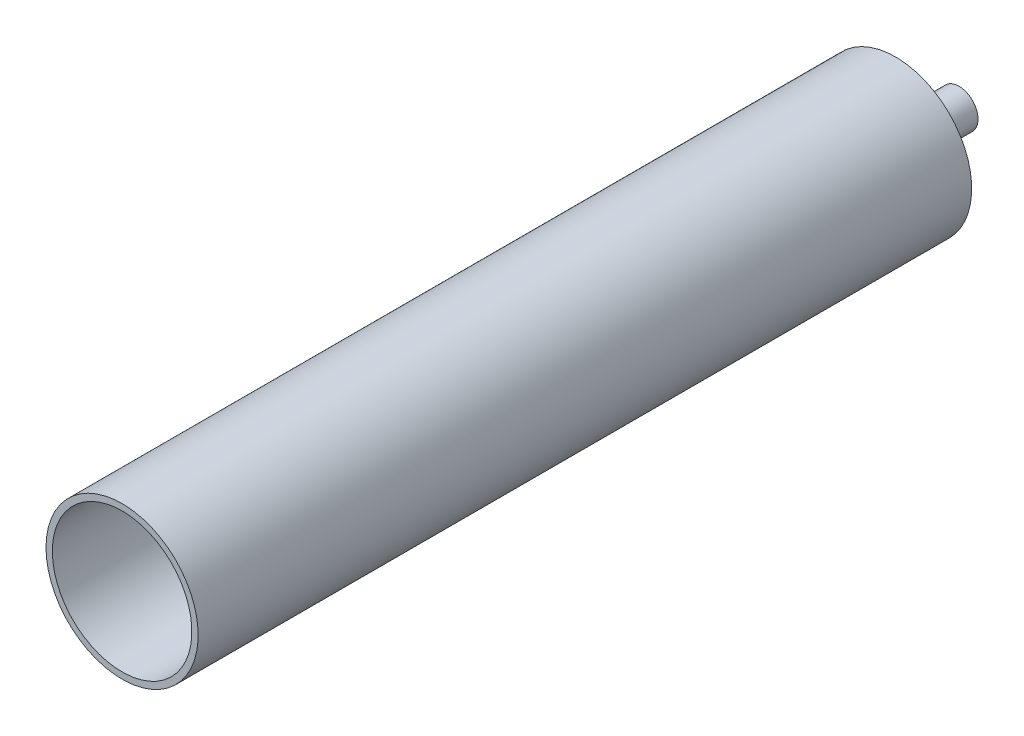
SolidWorks part; units mm, degrees
ref_plane "Front" through (0, 0, 0) normal (0, 0, 1) x (1, 0, 0)
ref_plane "Top" through (0, 0, 0) normal (0, 1, 0) x (1, 0, 0)
ref_plane "Right" through (0, 0, 0) normal (1, 0, 0) x (0, 0, -1)
sketch "Sketch1" plane through (0, 0, 0) normal (0, 0, 1) x (1, 0, 0)
  circle A0 centre (0, 0) radius 7.62
  circle A1 centre (0, 0) radius 6.985
  dimension "D1" = 15.24
  dimension "D2" = 13.97
extrude "Boss-Extrude1" add sketch "Sketch1" along normal blind 76.2
sketch "Sketch2" plane through (0, 0, 0) normal (0, 0, -1) x (-1, 0, 0)
  circle A0 centre (0, 0) radius 7.62
extrude "Boss-Extrude2" add sketch "Sketch2" along normal blind 1.27
sketch "Sketch3" plane through (0, 0, -1.27) normal (0, 0, -1) x (-1, 0, 0)
  circle A0 centre (0, 0) radius 1.905
  circle A1 centre (0, 0) radius 1.27
  dimension "D1" = 3.81
  dimension "D2" = 2.54
extrude "Boss-Extrude3" add sketch "Sketch3" along normal blind 6.35 and the other way up to surface (1.27 mm away) other way up to face at (6.985, 0, 0)
sketch "Sketch4" plane through (0, 0, -1.27) normal (0, 0, -1) x (-1, 0, 0)
  circle A0 centre (0, 0) radius 1.27
  dimension "D1" = 2.54
extrude "Cut-Extrude1" cut sketch "Sketch4" against normal up to surface (1.27 mm away) up to face at (6.985, 0, 0)
